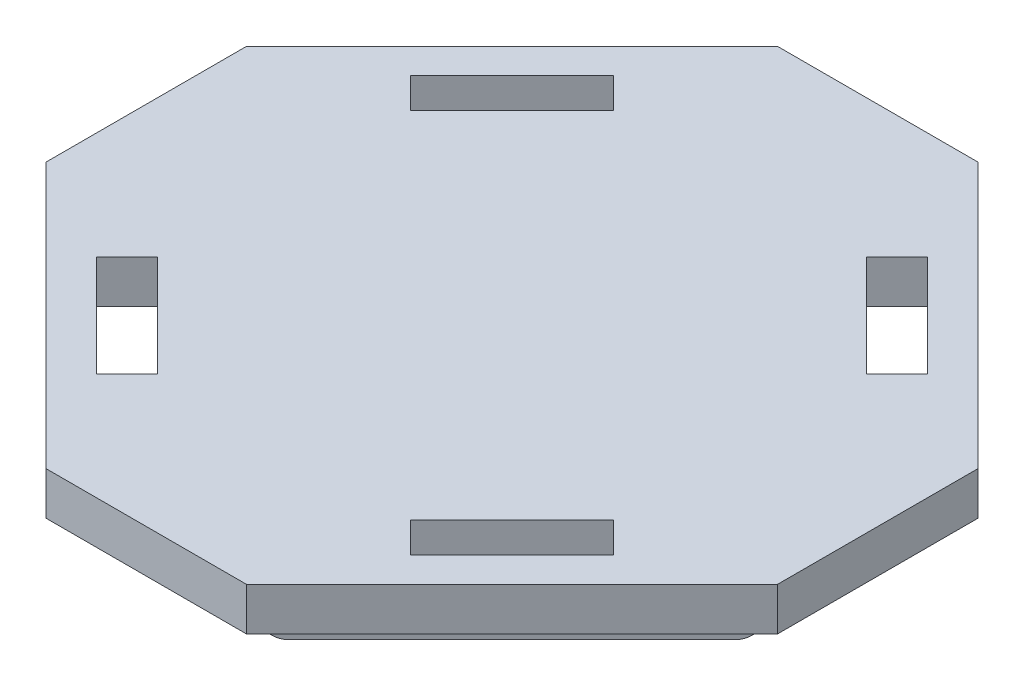
SolidWorks part; units mm, degrees
other "Bottom Plate" parameters "D1"=2.5518, "D2"=2.5518, "D3"=7.3498, "D4"=6, "D5"=3
ref_plane "Front Plane" through (0, 0, 0) normal (0, 0, 1) x (1, 0, 0)
ref_plane "Top Plane" through (0, 0, 0) normal (0, 1, 0) x (1, 0, 0)
ref_plane "Right Plane" through (0, 0, 0) normal (1, 0, 0) x (0, 0, -1)
sketch "Sketch1" plane through (0, 0, 0) normal (0, 1, 0) x (1, 0, 0)
  line L0 (-7, 25.5269) -> (7, 25.5269)
  line L1 (7, 25.5269) -> (25.5269, 7)
  line L2 (25.5269, 7) -> (25.5269, -7)
  line L3 (25.5269, -7) -> (7, -25.5269)
  line L4 (7, -25.5269) -> (-7, -25.5269)
  line L5 (-7, -25.5269) -> (-25.5269, -7)
  line L6 (-25.5269, -7) -> (-25.5269, 7)
  line L7 (-25.5269, 7) -> (-7, 25.5269)
  point P2 (0, 25.5269)
  point P9 (0, -25.5269)
  point P11 (-25.5269, 0)
  point P12 (25.5269, 0)
  dimension "D1" = 14
  dimension "D2" = 14
  dimension "D3" = 46
extrude "Main Plate" add sketch "Sketch1" along normal blind 3
sketch "Sketch2" plane through (0, 0, 0) normal (0, -1, 0) x (1, 0, 0)
  line L0 (10.9602, 18.0312) -> (18.0312, 10.9602)
  line L1 (18.0312, 10.9602) -> (15.9099, 8.8388)
  line L2 (15.9099, 8.8388) -> (8.8388, 15.9099)
  line L3 (8.8388, 15.9099) -> (10.9602, 18.0312)
  line L4 (0, 0) -> (16.2635, 16.2635) construction
  line L5 (7, 25.5269) -> (25.5269, 7) construction
  line L6 (8.8388, -15.9099) -> (15.9099, -8.8388)
  line L7 (15.9099, -8.8388) -> (18.0312, -10.9602)
  line L8 (18.0312, -10.9602) -> (10.9602, -18.0312)
  line L9 (10.9602, -18.0312) -> (8.8388, -15.9099)
  line L10 (-15.9099, -8.8388) -> (-8.8388, -15.9099)
  line L11 (-8.8388, -15.9099) -> (-10.9602, -18.0312)
  line L12 (-10.9602, -18.0312) -> (-18.0312, -10.9602)
  line L13 (-18.0312, -10.9602) -> (-15.9099, -8.8388)
  line L14 (-8.8388, 15.9099) -> (-15.9099, 8.8388)
  line L15 (-15.9099, 8.8388) -> (-18.0312, 10.9602)
  line L16 (-18.0312, 10.9602) -> (-10.9602, 18.0312)
  line L17 (-10.9602, 18.0312) -> (-8.8388, 15.9099)
  point P9 (12.3744, 12.3744)
  point P25 (0, 0)
  dimension "D1" = 3
  dimension "D2" = 10
  dimension "D3" = 17.5
  dimension "D4" = 4
extrude "Top Plate Connector Holes" cut sketch "Sketch2" against normal through all
sketch "Sketch3" plane through (0, 0, 0) normal (0, -1, 0) x (1, 0, 0)
  line L0 (1.7678, 19.4454) -> (19.4454, 1.7678)
  line L1 (19.4454, 1.7678) -> (17.3241, -0.3536)
  line L2 (17.3241, -0.3536) -> (-0.3536, 17.3241)
  line L3 (-0.3536, 17.3241) -> (1.7678, 19.4454)
  line L4 (0, 0) -> (16.2635, 16.2635) construction
  line L5 (7, 25.5269) -> (25.5269, 7) construction
  line L6 (-16.2635, 16.2635) -> (16.2635, -16.2635) construction
  line L7 (-25.5269, 7) -> (-7, 25.5269) construction
  line L8 (25.5269, -7) -> (7, -25.5269) construction
  line L9 (-1.7678, -19.4454) -> (0.3536, -17.3241)
  line L10 (0.3536, -17.3241) -> (-17.3241, 0.3536)
  line L11 (-19.4454, -1.7678) -> (-1.7678, -19.4454)
  line L12 (-17.3241, 0.3536) -> (-19.4454, -1.7678)
  point P9 (10.6066, 10.6066)
  dimension "D1" = 3
  dimension "D2" = 25
  dimension "D3" = 12
extrude "ZipTie Structure" add sketch "Sketch3" along normal blind 6
sketch "Sketch5" plane through (-10.6066, 0, -10.6066) normal (-0.7071, 0, -0.7071) x (-0.7071, 0, 0.7071)
  line L0 (12.5, 0) -> (-12.5, 0) construction
  line L1 (-9.5, 0) -> (-2, 0)
  line L2 (-9.5, 0) -> (-9.5, -3)
  line L3 (-9.5, -3) -> (-2, -3)
  line L4 (-2, 0) -> (-2, -3)
  line L5 (-12.5, -6) -> (-12.5, 0) construction
  line L6 (2, 0) -> (9.5, 0)
  line L7 (2, 0) -> (2, -3)
  line L8 (2, -3) -> (9.5, -3)
  line L9 (9.5, 0) -> (9.5, -3)
  line L10 (12.5, -6) -> (12.5, 0) construction
  dimension "D1" = 3
  dimension "D2" = 7.5
  dimension "D3" = 7.5
  dimension "D4" = 3
  dimension "D5" = 3
extrude "ZipTie Holes" cut sketch "Sketch5" against normal through all
fillet "Removing Stress Concentrations" radius 1.5 30 edges at (8.1317, -3, 10.9602) (10.9602, -3, 8.1317) (16.2635, -3, 2.8284) (-2.8284, -3, -16.2635) (-8.1317, -3, -10.9602) (-10.9602, -3, -8.1317) (-16.2635, -3, -2.8284) (2.8284, -3, 16.2635) (-16.2635, 0, -2.8284) (-8.1317, 0, -10.9602) (-0.7071, 0, -18.3848) (2.8284, 0, 18.3848) (10.6066, 0, 10.6066) (18.3848, 0, 2.8284) (10.9602, 0, 8.1317) (2.8284, 0, 16.2635) (0.7071, -6, 18.3848) (18.3848, -6, 0.7071) (18.3848, 0, 0.7071) (16.2635, 0, 2.8284) (0.7071, 0, 18.3848) (8.1317, 0, 10.9602) (-18.3848, 0, -0.7071) (-2.8284, 0, -16.2635) (-10.9602, 0, -8.1317) (-2.8284, 0, -18.3848) (-10.6066, 0, -10.6066) (-18.3848, 0, -2.8284) (-18.3848, -6, -0.7071) (-0.7071, -6, -18.3848)
equation "\"D3@Sketch5\"=\"D2@Sketch5\""
